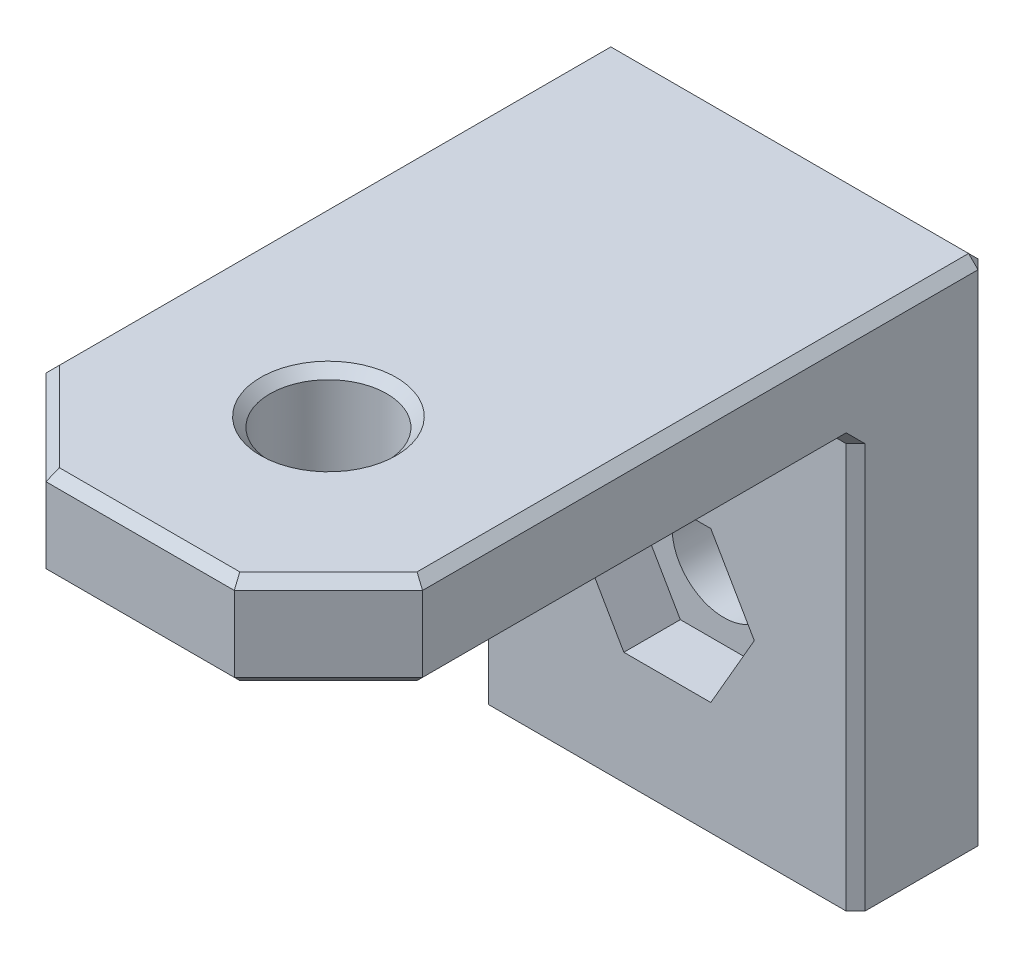
SolidWorks part; units mm, degrees
note: The reader was unsure of these and kept them because the rebuilt part matched: shared geometry of "草图1<3>".
ref_plane "前视基准面" through (0, 0, 0) normal (0, 0, 1) x (1, 0, 0)
ref_plane "上视基准面" through (0, 0, 0) normal (0, 1, 0) x (1, 0, 0)
ref_plane "右视基准面" through (0, 0, 0) normal (1, 0, 0) x (0, 0, -1)
other "Configuration Table"
sketch "草图1" plane through (0, 0, 0) normal (0, 1, 0) x (1, 0, 0)
  line L0 (0, 28) -> (20, 28)
  line L5 (0, 0) -> (20, 0)
  line L6 (0, 0) -> (0, 35)
  line L7 (0, 35) -> (20, 35)
  line L8 (20, 0) -> (20, 35)
  dimension "D1" = 20
  dimension "D2" = 35
  dimension "D3" = 7
extrude "凸台-拉伸1" add sketch "草图1" against normal blind 5 contours L5 L8 L0 L6
extrude "凸台-拉伸2" add sketch "草图1<3>" against normal blind 27 contours L0 L8 L7 L6
sketch "草图1<3>" plane through (0, 0, 0) normal (0, 1, 0) x (1, 0, 0) same geometry as "草图1"
sketch "草图2" plane through (0, -5, 0) normal (0, -1, 0) x (1, 0, 0)
  line L0 (10, 0) -> (10, -10) construction
  line L1 (0, 0) -> (20, 0) construction
  circle A0 centre (10, -10) radius 5
  dimension "D1" = 10
  dimension "D2" = 10
extrude "凸台-拉伸3" add sketch "草图2" along normal blind 2
sketch "草图4" plane through (0, 0, -35) normal (0, 0, -1) x (-1, 0, 0)
  line L0 (-10, -27) -> (-10, -17) construction
  line L1 (0, -27) -> (-20, -27) construction
  line L3 (-13.5, -20.5) -> (-6.5, -20.5)
  line L4 (-13.5, -20.5) -> (-13.5, -13.5)
  line L5 (-13.5, -13.5) -> (-6.5, -13.5)
  line L6 (-6.5, -20.5) -> (-6.5, -13.5)
  line L7 (-13.5, -20.5) -> (-6.5, -13.5) construction
  line L8 (-13.5, -13.5) -> (-6.5, -20.5) construction
  dimension "D1" = 10
  dimension "D2" = 7
  dimension "D3" = 7
sketch "草图5" plane through (0, 0, -35) normal (0, 0, -1) x (-1, 0, 0)
  line L0 (-10, -27) -> (-10, -17)
  line L1 (0, -27) -> (-20, -27) construction
  circle A0 centre (-10, -17) radius 2.75
  dimension "D2" = 5.5
  dimension "D1" = 10
extrude "切除-拉伸2" cut sketch "草图5" against normal through all
fillet "圆角1" radius 1 1 edges at (10, -5, -5)
sketch "草图6" plane through (0, -7, 0) normal (0, -1, 0) x (1, 0, 0)
  circle A0 centre (10, -10) radius 3.1
  dimension "D1" = 6.2
extrude "切除-拉伸3" cut sketch "草图6" against normal through all
sketch "草图7" plane through (0, 0, -28) normal (0, 0, 1) x (1, 0, 0)
  line L1 (14.6188, -17) -> (12.3094, -13)
  line L2 (12.3094, -13) -> (7.6906, -13)
  line L3 (7.6906, -13) -> (5.3812, -17)
  line L4 (5.3812, -17) -> (7.6906, -21)
  line L5 (7.6906, -21) -> (12.3094, -21)
  line L6 (12.3094, -21) -> (14.6188, -17)
  circle A0 centre (10, -17) radius 4 construction
  dimension "D1" = 8
extrude "切除-拉伸4" cut sketch "草图7" against normal blind 3
chamfer "倒角1" distance 5 angle 45 2 edges at (20, -2.5, 0) (0, -2.5, 0)
chamfer "倒角2" distance 0.5 angle 45 19 edges at (7.25, -17, -35) (0, -16, -28) (20, -16, -28) (10, -5, -28) (0, -5, -16.5) (2.5, -5, -2.5) (10, -5, 0) (17.5, -5, -2.5) (20, -5, -16.5) (0, -13.5, -35) (10, -27, -35) (20, -13.5, -35) (2.5, 0, -2.5) (0, 0, -20) (10, 0, -35) (20, 0, -20) (17.5, 0, -2.5) (10, 0, 0) (10, 0, -13.1)
